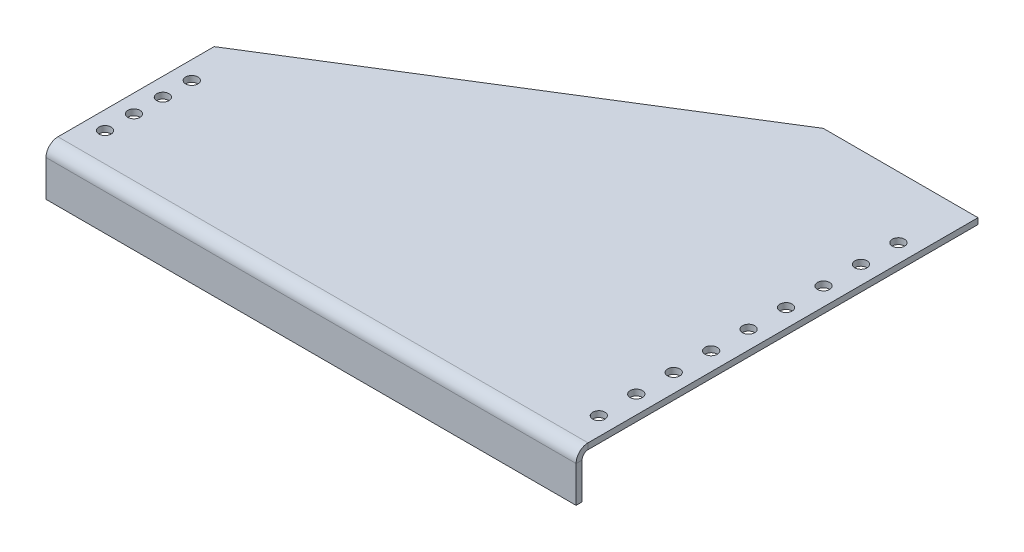
SolidWorks part; units mm, degrees
note: The reader was unsure of these and kept them because the rebuilt part matched: thickness of "Base-Flange1", "Edge-Flange4", "Sheet-Metal2", "Sheet-Metal6", "Sheet-Metal7", "Sheet-Metal8", "Sheet-Metal9"; flange length of "Edge-Flange4".
ref_plane "Front Plane" through (0, 0, 0) normal (0, 0, 1) x (1, 0, 0)
ref_plane "Top Plane" through (0, 0, 0) normal (0, 1, 0) x (1, 0, 0)
ref_plane "Right Plane" through (0, 0, 0) normal (1, 0, 0) x (0, 0, -1)
sketch "Sketch1" plane through (0, 0, 0) normal (0, 1, 0) x (1, 0, 0)
  line L0 (120.078, 68.707) -> (120.078, -85.3208) construction
  line L1 (120.078, -87.757) -> (-89.398, -87.757)
  line L2 (120.078, -87.757) -> (120.078, 87.757)
  line L3 (120.078, 87.757) -> (-89.398, 87.757)
  line L4 (-89.398, -87.757) -> (-89.398, 87.757)
  line L5 (120.078, -87.757) -> (-89.398, 87.757) construction
  line L6 (120.078, 87.757) -> (-89.398, -87.757) construction
  line L7 (-89.398, -90.1192) -> (-89.398, -26.6192) construction
  point P8 (0, 0)
  point P9 (0, 0)
  dimension "D2" = 175.514
base flange "Base-Flange1" sketch "Sketch1" thickness 2.3622 reverse thickness direction no parameters "D1"=10
edge flange "Edge-Flange4" sketch "Sketch35" flange angle 90 flange length 19.05 flange position material outside bend radius 2.36 thickness 2.3622 relief rectangular parameters "D6"=10
bend "EdgeBend9" bend radius 2.36 bend angle 90 parameters "D5"=1
sketch "Sketch35" plane through (0, -2.3622, 87.757) normal (0, 0, 1) x (-1, 0, 0)
  line L0 (89.398, 0) -> (-120.078, 0) construction
  line L1 (89.398, 0) -> (-120.078, 0)
  line L2 (-120.078, 0) -> (-120.078, 16.6878)
  line L3 (-120.078, 16.6878) -> (89.398, 16.6878)
  line L4 (89.398, 16.6878) -> (89.398, 0)
sketch "Sketch36" plane through (0, -2.3622, 0) normal (0, -1, 0) x (1, 0, 0)
  line L6 (-94.1202, 26.6192) -> (58.938, -68.707)
  line L9 (58.938, -68.707) -> (140.0226, -68.707)
  line L12 (140.0226, -68.707) -> (140.0226, -102.5742)
  line L14 (140.0226, -102.5742) -> (-121.9312, -102.5742)
  line L15 (-121.9312, -102.5742) -> (-121.9312, 26.6192)
  line L16 (-121.9312, 26.6192) -> (-94.1202, 26.6192)
  point P2 (-110.6402, 21.897)
extrude "Cut-Extrude1" cut sketch "Sketch36" against normal through all normal cut yes
sketch "Sketch38" plane through (0, -2.3622, 0) normal (0, -1, 0) x (1, 0, 0)
  circle A0 centre (-82.2341, 73.967) radius 2.413
  circle A1 centre (-82.2341, 62.537) radius 2.413
  circle A2 centre (-82.2341, 51.107) radius 2.413
  circle A3 centre (-82.2341, 39.677) radius 2.413
extrude "Cut-Extrude2" cut sketch "Sketch38" against normal through all normal cut yes
sketch "Sketch39" plane through (0, -2.3622, 0) normal (0, -1, 0) x (1, 0, 0)
  circle A0 centre (112.9141, 73.967) radius 2.413
  circle A1 centre (112.9141, 59.1689) radius 2.413
  circle A2 centre (112.9141, 44.3708) radius 2.413
  circle A3 centre (112.9141, 29.5727) radius 2.413
  circle A4 centre (112.9141, 14.7746) radius 2.413
  circle A5 centre (112.9141, -0.0234) radius 2.413
  circle A6 centre (112.9141, -14.8215) radius 2.413
  circle A7 centre (112.9141, -29.6196) radius 2.413
  circle A8 centre (112.9141, -44.4177) radius 2.413
extrude "Cut-Extrude3" cut sketch "Sketch39" against normal through all normal cut yes
sketch "Bend-Lines1" [suppressed] plane through (0, 0, 0) normal (0, 1, 0) x (1, 0, 0)
sketch "Bounding-Box1" [suppressed] plane through (0, 0, 0) normal (0, 1, 0) x (1, 0, 0)
sheet metal parameters "Sheet-Metal2" thickness 2.3622 parameters "D1"=10
flat pattern "Flat-Pattern2" [suppressed]
sketch "Bend-Lines2" plane through (0, 0, 0) normal (0, 1, 0) x (1, 0, 0)
sketch3d "Bounding-Box2" [suppressed]
  line L0 (101.6, -88.9, 0) -> (-101.6, -88.9, 0) construction
  line L1 (101.6, 88.9, 0) -> (-101.6, 88.9, 0) construction
  line L2 (101.6, -88.9, 0) -> (101.6, 88.9, 0) construction
  line L3 (-101.6, -88.9, 0) -> (-101.6, 88.9, 0) construction
sheet metal parameters "Sheet-Metal6" thickness 2.3622 parameters "D1"=10
flat pattern "Flat-Pattern2"
sketch "Bend-Lines2" plane through (0, 0, 0) normal (0, 1, 0) x (1, 0, 0)
  line L0 (-105.918, -88.1782) -> (105.918, -88.1782) construction
  line L1 (-105.918, -88.1782) -> (105.918, -88.1782) construction
sketch3d "Bounding-Box2" [suppressed]
  line L0 (105.918, -105.2871, 0) -> (-105.918, -105.2871, 0) construction
  line L1 (105.918, 87.757, 0) -> (-105.918, 87.757, 0) construction
  line L2 (105.918, -105.2871, 0) -> (105.918, 87.757, 0) construction
  line L3 (-105.918, -105.2871, 0) -> (-105.918, 87.757, 0) construction
bend of the flat pattern "Flatten-<EdgeBend9>1"
sheet metal parameters "Sheet-Metal7" thickness 2.3622 parameters "D1"=10
flat pattern "Flat-Pattern2"
sketch "Bend-Lines2" plane through (0, 0, 0) normal (0, 1, 0) x (1, 0, 0)
  line L0 (-89.398, -88.1782) -> (120.078, -88.1782) construction
  line L1 (-89.398, -88.1782) -> (120.078, -88.1782) construction
sketch3d "Bounding-Box2" [suppressed]
  line L0 (120.078, -105.2871, 0) -> (-89.398, -105.2871, 0) construction
  line L1 (120.078, 68.707, 0) -> (-89.398, 68.707, 0) construction
  line L2 (120.078, -105.2871, 0) -> (120.078, 68.707, 0) construction
  line L3 (-89.398, -105.2871, 0) -> (-89.398, 68.707, 0) construction
bend of the flat pattern "Flatten-<EdgeBend9>1"
sheet metal parameters "Sheet-Metal8" thickness 2.3622 parameters "D1"=10
flat pattern "Flat-Pattern2"
sketch "Bend-Lines2" plane through (0, 0, 0) normal (0, 1, 0) x (1, 0, 0)
  line L0 (-89.398, -88.1782) -> (120.078, -88.1782) construction
  line L1 (-89.398, -88.1782) -> (120.078, -88.1782) construction
sketch3d "Bounding-Box2" [suppressed]
  line L0 (120.078, -105.2871, 0) -> (-89.398, -105.2871, 0) construction
  line L1 (120.078, 68.707, 0) -> (-89.398, 68.707, 0) construction
  line L2 (120.078, -105.2871, 0) -> (120.078, 68.707, 0) construction
  line L3 (-89.398, -105.2871, 0) -> (-89.398, 68.707, 0) construction
bend of the flat pattern "Flatten-<EdgeBend9>1"
sheet metal parameters "Sheet-Metal9" thickness 2.3622 parameters "D1"=10
flat pattern "Flat-Pattern2"
sketch "Bend-Lines2" plane through (0, 0, 0) normal (0, 1, 0) x (1, 0, 0)
  line L0 (-89.398, -88.1782) -> (120.078, -88.1782) construction
  line L1 (-89.398, -88.1782) -> (120.078, -88.1782) construction
sketch3d "Bounding-Box2" [suppressed]
  line L0 (120.078, -105.2871, 0) -> (-89.398, -105.2871, 0) construction
  line L1 (120.078, 68.707, 0) -> (-89.398, 68.707, 0) construction
  line L2 (120.078, -105.2871, 0) -> (120.078, 68.707, 0) construction
  line L3 (-89.398, -105.2871, 0) -> (-89.398, 68.707, 0) construction
bend of the flat pattern "Flatten-<EdgeBend9>1"
